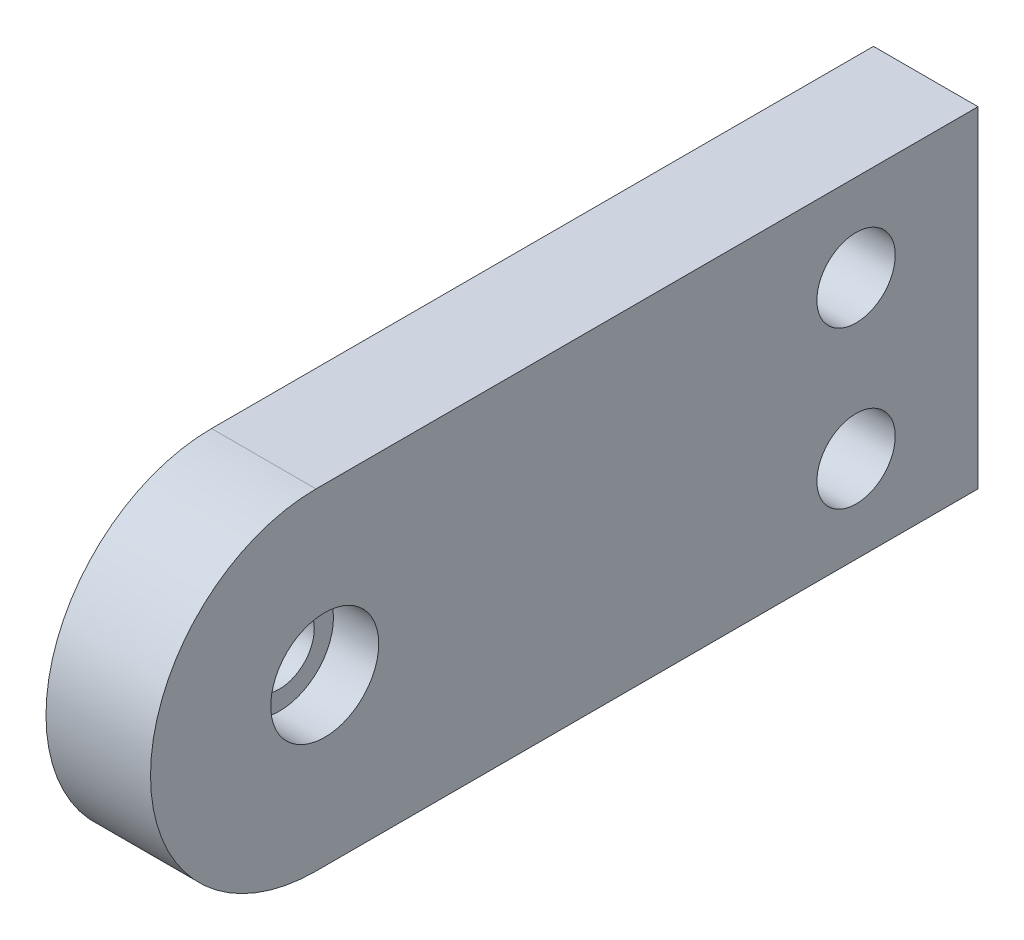
SolidWorks part; units mm, degrees
ref_plane "前视基准面" through (0, 0, 0) normal (0, 0, 1) x (1, 0, 0)
ref_plane "上视基准面" through (0, 0, 0) normal (0, 1, 0) x (1, 0, 0)
ref_plane "右视基准面" through (0, 0, 0) normal (1, 0, 0) x (0, 0, -1)
other "Configuration Table"
sketch "草图1" plane through (0, 0, 0) normal (1, 0, 0) x (0, 0, -1)
  line L0 (-150, 0) -> (150, 0) construction
  line L1 (-125, 14.5) -> (125, 14.5)
  line L2 (-125, 14.5) -> (-125, -14.5)
  line L3 (-125, -14.5) -> (125, -14.5)
  line L4 (125, 14.5) -> (125, -14.5)
  line L5 (-72.5, 29.5) -> (-72.5, 25.5)
  line L6 (-75, 14.5) -> (-45, 14.5)
  line L7 (-75, 14.5) -> (-75, 29.5)
  line L8 (-120, 10.8586) -> (120, 10.8586)
  line L9 (-120, 10.8586) -> (-120, -10.8586)
  line L10 (-120, -10.8586) -> (120, -10.8586)
  line L11 (120, 10.8586) -> (120, -10.8586)
  line L12 (-120, 10.8586) -> (120, -10.8586) construction
  line L13 (-120, -10.8586) -> (120, 10.8586) construction
  line L14 (-75, 29.5) -> (-45, 29.5)
  line L15 (-45, 14.5) -> (-45, 29.5)
  line L16 (-15, 14.5) -> (15, 14.5)
  line L17 (-15, 14.5) -> (-15, 29.5)
  line L18 (-15, 29.5) -> (15, 29.5)
  line L19 (15, 14.5) -> (15, 29.5)
  line L20 (45, 14.5) -> (75, 14.5)
  line L21 (45, 14.5) -> (45, 29.5)
  line L22 (45, 29.5) -> (75, 29.5)
  line L23 (75, 14.5) -> (75, 29.5)
  line L24 (-47.5, 29.5) -> (-47.5, 25.5)
  line L25 (-12.5, 29.5) -> (-12.5, 25.5)
  line L26 (12.5, 29.5) -> (12.5, 25.5)
  line L27 (47.5, 29.5) -> (47.5, 25.5)
  line L29 (72.5, 25.5) -> (72.5, 29.5)
  circle A2 centre (-67.5, -10.8586) radius 2
  circle A3 centre (-22.5, -10.8586) radius 2
  circle A4 centre (22.5, -10.8586) radius 2
  circle A5 centre (-60, 25.5) radius 2
  circle A6 centre (67.5, -10.8586) radius 2
  circle A7 centre (0, 25.5) radius 2
  circle A8 centre (60, 25.5) radius 2
  circle A9 centre (-60, 25.5) radius 12.5
  circle A10 centre (0, 25.5) radius 12.5
  circle A11 centre (60, 25.5) radius 12.5
  circle A12 centre (-67.5, -10.8586) radius 12.5
  circle A13 centre (-22.5, -10.8586) radius 12.5
  circle A14 centre (22.5, -10.8586) radius 12.5
  circle A15 centre (67.5, -10.8586) radius 12.5
  circle A16 centre (150, 0) radius 2
  circle A17 centre (-150, 0) radius 2
  circle A18 centre (-150, 0) radius 3.1
  point P10 (0, 0)
  point P12 (-125, 0)
  point P56 (-60, 29.5)
  point P62 (0, 29.5)
  point P64 (60, 29.5)
  dimension "D2" = 5
  dimension "D4" = 25
  dimension "D8" = 4
  dimension "D18" = 4
  dimension "D22" = 6.2
  dimension "D1" = 300
  dimension "D3" = 5
  dimension "D5" = 14.5
  dimension "D6" = 120
  dimension "D7" = 10.8586
  dimension "D9" = 52.5
  dimension "D10" = 45
  dimension "D11" = 45
  dimension "D12" = 45
  dimension "D13" = 60
  dimension "D14" = 60
  dimension "D15" = 60
  dimension "D16" = 60
  dimension "D17" = 52.5
  dimension "D19" = 30
  dimension "D20" = 4
  dimension "D21" = 15
extrude "凸台-拉伸1" add sketch "草图1" along normal blind 28 contours L1 L4 L3 L2 | L14 L15 L6 L7 | L18 L19 L16 L17 | L22 L23 L20 L21
extrude "切除-拉伸1" cut sketch "草图1<3>" along normal through all contours A2 | A3 | A4 | A6 | A8 | A7 | A5
sketch "草图1<3>" plane through (0, 0, 0) normal (1, 0, 0) x (0, 0, -1) same geometry as "草图1"
extrude "切除-拉伸2" cut sketch "草图1<5>" along normal offset from surface (24 mm away) 2 from offset 2 contours A9 L14 L5 | A9 L24 L14 | A10 L18 L25 | A10 L26 L18 | A11 L22 L27 | A11 L29 L22 | A12 | A9 | A13 | A10 | A14 | A11 | A15 region at (0, 28.5053, 72.3037) region at (0, 28.5053, 47.6963) region at (0, 28.5053, 12.3037) region at (0, 28.5053, -12.3037) region at (0, 28.5053, -47.6963) region at (0, 28.5053, -72.3037) up to face at (28, -10.8586, 65.5)
sketch "草图1<5>" plane through (0, 0, 0) normal (1, 0, 0) x (0, 0, -1) same geometry as "草图1"
sketch "草图3" plane through (0, 0, 125) normal (0, 0, 1) x (1, 0, 0)
  line L0 (28, 14.5) -> (28, -14.5) construction
  line L1 (28, 9.5) -> (22, 9.5)
  line L2 (28, 9.5) -> (28, -9.5)
  line L3 (28, -9.5) -> (22, -9.5)
  line L4 (22, 9.5) -> (22, -9.5)
  line L5 (28, 14.5) -> (0, 14.5) construction
  line L6 (28, -14.5) -> (0, -14.5) construction
  line L7 (0, 14.5) -> (0, -14.5) construction
  line L8 (0, 9.5) -> (6, 9.5)
  line L9 (0, 9.5) -> (0, -9.5)
  line L10 (0, -9.5) -> (6, -9.5)
  line L11 (6, 9.5) -> (6, -9.5)
  dimension "D1" = 6
  dimension "D2" = 5
  dimension "D3" = 5
extrude "凸台-拉伸2" add sketch "草图3" along normal blind 35 contours L1 L4 L3 L2
extrude "凸台-拉伸3" add sketch "草图3<3>" along normal blind 35 contours L2 L3 L4 L1 | L9 L10 L11 L8
sketch "草图3<3>" plane through (0, 0, 125) normal (0, 0, 1) x (1, 0, 0) same geometry as "草图3"
extrude "切除-拉伸3" cut sketch "草图1<6>" along normal through all contours A17
sketch "草图1<6>" plane through (0, 0, 0) normal (1, 0, 0) x (0, 0, -1) same geometry as "草图1"
extrude "切除-拉伸7" cut sketch "草图1<8>" along normal up to next contours A18
sketch "草图1<8>" plane through (0, 0, 0) normal (1, 0, 0) x (0, 0, -1) same geometry as "草图1"
fillet "圆角1" radius 9.5 4 edges at (25, 9.5, 160) (25, -9.5, 160) (3, -9.5, 160) (3, 9.5, 160)
fillet "圆角2" radius 5 2 edges at (14, -14.5, 125) (14, 14.5, 125)
sketch "草图4" plane through (0, 0, -125) normal (0, 0, -1) x (-1, 0, 0)
  line L1 (-28, 14.5) -> (0, 14.5) construction
  circle A0 centre (-14, 0) radius 5.1
  point P7 (-14, 14.5)
  dimension "D1" = 10.2
extrude "切除-拉伸4" cut sketch "草图4" against normal blind 31.5
extrude "切除-拉伸5" cut sketch "草图4<2>" against normal offset from surface (21.5 mm away) 10 flip side to cut up to face at (8.9, 0, -93.5)
sketch "草图4<2>" plane through (0, 0, -125) normal (0, 0, -1) x (-1, 0, 0) same geometry as "草图4"
sketch "草图5" plane through (0, 0, -103.5) normal (0, 0, -1) x (-1, 0, 0)
  line L0 (-28, 14.5) -> (0, 14.5) construction
  line L1 (-25.9, -12.4) -> (-2.1, -12.4)
  line L2 (-25.9, -12.4) -> (-25.9, 12.4)
  line L3 (-25.9, 12.4) -> (-2.1, 12.4)
  line L4 (-2.1, -12.4) -> (-2.1, 12.4)
  line L5 (-25.9, -12.4) -> (-2.1, 12.4) construction
  line L6 (-25.9, 12.4) -> (-2.1, -12.4) construction
  line L7 (0, -14.5) -> (0, 14.5) construction
  circle A0 centre (-14, 0) radius 5.1 construction
  point P0 (-14, 0)
  dimension "D1" = 2.1
  dimension "D2" = 2.1
extrude "切除-拉伸6" cut sketch "草图5" against normal blind 18 flip side to cut contours L3 L4 L1 L2
sketch "草图6" plane through (0, 14.5, 0) normal (0, 1, 0) x (1, 0, 0)
  circle A0 centre (7, 23.5) radius 0.75
  circle A1 centre (21, 35.5) radius 0.75
  circle A2 centre (7, -23.5) radius 0.75
  circle A3 centre (21, -35.5) radius 0.75
  dimension "D1" = 1.5
extrude "切除-拉伸8" cut sketch "草图6" against normal blind 4 contours A2 | A3 | A0 | A1
sketch "草图7" plane through (0, 14.5, 0) normal (0, 1, 0) x (1, 0, 0)
  circle A0 centre (7, -89.5) radius 0.75
  circle A1 centre (21.2, -110.5) radius 0.75
  dimension "D1" = 1.5
extrude "切除-拉伸9" cut sketch "草图7" against normal blind 4 contours A0 | A1
sketch "草图8" plane through (0, 0, 0) normal (-1, 0, 0) x (0, 0, 1)
  circle A0 centre (47, 4) radius 0.75
  circle A1 centre (2.499, -1.5) radius 0.75
  dimension "D1" = 1.5
extrude "切除-拉伸10" cut sketch "草图8" against normal blind 4
sketch "草图9" plane through (28, 0, 0) normal (1, 0, 0) x (0, 0, -1)
  circle A0 centre (-107.5, -0.5) radius 0.75
  circle A1 centre (-92.5, -0.5) radius 0.75
  dimension "D1" = 1.5
extrude "切除-拉伸11" cut sketch "草图9" against normal blind 4 contours A0 | A1
sketch "草图10" plane through (0, 0, 0) normal (-1, 0, 0) x (0, 0, 1)
  line L0 (30, 14.5) -> (0, -14.5)
  line L1 (45, 14.5) -> (15, 14.5) construction
  line L2 (120, -14.5) -> (-85.5, -14.5) construction
  line L3 (30, 14.5) -> (30, 45.5421)
  line L4 (30, 45.5421) -> (207.4503, 45.5421)
  line L5 (207.4503, 45.5421) -> (207.4503, -65.6361)
  line L6 (207.4503, -65.6361) -> (0, -65.6361)
  line L7 (0, -65.6361) -> (0, -14.5)
  line L8 (30, 45.5421) -> (-140.4585, 45.5421)
  line L9 (30, 14.5) -> (-10, 14.5)
  line L10 (30, 14.5) -> (30, -14.5)
  line L11 (30, -14.5) -> (-10, -14.5)
  line L12 (-10, 14.5) -> (-10, -14.5)
  line L13 (-140.4585, 45.5421) -> (-140.4585, -65.6361)
  line L14 (-140.4585, -65.6361) -> (-10, -65.6361)
  line L15 (-10, -65.6361) -> (-10, -14.5)
  circle M8 centre (2.499, -1.5) radius 0.75
  circle M12 centre (0, 25.5) radius 2
  circle M13 centre (-60, 25.5) radius 2
  circle M14 centre (-67.5, -10.8586) radius 2
  circle M15 centre (-22.5, -10.8586) radius 2
  line M17 (-85.5, 14.5) -> (-85.5, -14.5)
  line M18 (-85.5, -14.5) -> (120, -14.5)
  line M29 (45, 14.5) -> (15, 14.5)
  line M30 (15, 14.5) -> (15, 29.5)
  line M31 (15, 29.5) -> (-15, 29.5)
  line M32 (-15, 29.5) -> (-15, 14.5)
  line M33 (-15, 14.5) -> (-45, 14.5)
  line M34 (-45, 14.5) -> (-45, 29.5)
  line M35 (-45, 29.5) -> (-75, 29.5)
  line M36 (-75, 29.5) -> (-75, 14.5)
  line M37 (-75, 14.5) -> (-85.5, 14.5)
  dimension "D1" = 40
sketch "草图11" plane through (0, 0, 0) normal (1, 0, 0) x (0, 0, -1)
  line L0 (-30, 14.5) -> (0, -14.5) construction
  line L1 (-45, 14.5) -> (-15, 14.5) construction
  line L2 (-120, -14.5) -> (85.5, -14.5) construction
  circle A0 centre (-14.5301, 6.5) radius 0.75
  circle A1 centre (-1.0818, -6.5) radius 0.75
  circle A2 centre (-14.5301, 6.5) radius 2.5
  circle A3 centre (-1.0818, -6.5) radius 2.5
  circle A4 centre (-14.5301, 6.5) radius 1.8
  circle A5 centre (-1.0818, -6.5) radius 1.8
  circle A6 centre (5.4699, 6.5) radius 0.75
  circle A7 centre (5.4699, 6.5) radius 2.5
  circle A8 centre (5.4699, 6.5) radius 1.8
  dimension "D3" = 1.5
  dimension "D4" = 3.6
  dimension "D5" = 5
  dimension "D1" = 5
  dimension "D2" = 5
  dimension "D6" = 8
  dimension "D7" = 8
  dimension "D8" = 20
extrude "切除-拉伸12" cut sketch "草图11" along normal through all contours A1 | A0 | A6
extrude "切除-拉伸14" cut sketch "草图10" against normal through all contours L14 L15 L3 L8 L13 M18 M17 M37 M36 M35 M34 M33 M32 M31 M30 M29 | L12 L9 M30 M31 M32 M33 M34 M35 M36 M37 M17 M18 M12 M14 M15 M13 region at (0, 16.5351, 22.5) region at (0, 6.3937, -42.6633)
extrude "切除-拉伸15" cut sketch "草图10<5>" against normal blind 4.1 contours L9 L12 L0 M18 M29 M8 region at (0, 2.9108, 4.0037)
sketch "草图10<5>" plane through (0, 0, 0) normal (-1, 0, 0) x (0, 0, 1) same geometry as "草图10"
extrude "切除-拉伸16" cut sketch "草图10<6>" along normal blind 4.1 from surface contours L9 L12 L0 M18 M29 M8 | M8 region at (0, 2.9108, 4.0037) region at (0, -1.5, 2.499) starting at face at (28, 6.7692, 90.5389)
sketch "草图10<6>" plane through (0, 0, 0) normal (-1, 0, 0) x (0, 0, 1) same geometry as "草图10"
sketch "草图13" plane through (0, 14.5, 0) normal (0, 1, 0) x (1, 0, 0)
  line L0 (4.1, -30) -> (0, -30) construction
  line L1 (4.1, -30) -> (23.9, -30)
  line L2 (4.1, -30) -> (4.1, 10)
  line L3 (4.1, 10) -> (23.9, 10)
  line L4 (23.9, -30) -> (23.9, 10)
  line L5 (4.1, -30) -> (4.1, -5.9372) construction
extrude "切除-拉伸17" cut sketch "草图13" against normal blind 4.1
sketch "草图14" plane through (0, -14.5, 0) normal (0, -1, 0) x (1, 0, 0)
  line L0 (4.1, 0) -> (0, 0) construction
  line L1 (4.1, 0) -> (23.9, 0)
  line L2 (4.1, 0) -> (4.1, -10)
  line L3 (4.1, -10) -> (23.9, -10)
  line L4 (23.9, 0) -> (23.9, -10)
  line L5 (4.1, -10) -> (4.1, 0) construction
extrude "切除-拉伸18" cut sketch "草图14" against normal blind 4.1
sketch "草图15" plane through (0, 0, 0) normal (-1, 0, 0) x (0, 0, 1)
  line L0 (0, -10.4) -> (0, -14.5)
  line L1 (0, -14.5) -> (4.2414, -10.4)
  line L2 (30, 14.5) -> (0, -14.5) construction
  line L4 (4.2414, -10.4) -> (0, -10.4)
  line L5 (0, -10.4) -> (-10, -10.4) construction
extrude "切除-拉伸19" cut sketch "草图15" against normal through all
sketch "草图16" plane through (0, 29.5, 0) normal (0, 1, 0) x (1, 0, 0)
  line L0 (28, -75) -> (0, -75) construction
  line L1 (6, -77.5) -> (22, -77.5)
  line L2 (6, -77.5) -> (6, -72.5)
  line L3 (6, -72.5) -> (22, -72.5)
  line L4 (22, -77.5) -> (22, -72.5)
  line L5 (6, -77.5) -> (22, -72.5) construction
  line L6 (6, -72.5) -> (22, -77.5) construction
  line L7 (26, -72.5) -> (2, -72.5) construction
  line L8 (26, -47.5) -> (26, -72.5) construction
  line L9 (6, -72.5) -> (22, -72.5)
  line L10 (6, -72.5) -> (6, -60)
  line L11 (6, -60) -> (22, -60)
  line L12 (22, -72.5) -> (22, -60)
  point P0 (14, -75)
  point P7 (14, -75)
  point P14 (26, -60)
  line M10 (0, -75) -> (28, -75)
  line M13 (26, -72.5) -> (2, -72.5)
  dimension "D1" = 16
extrude "切除-拉伸20" cut sketch "草图16" against normal blind 3 contours L1 L4 L2 M10 | L4 L2 M10 M13 | L12 L11 L10 M13 region at (14, 29.5, 76.25) region at (14, 29.5, 73.75) region at (14, 29.5, 66.25)
sketch "草图18" plane through (28, 0, 0) normal (1, 0, 0) x (0, 0, -1)
  line L0 (-150.5, 9.5) -> (-125, 9.5) construction
  line L1 (-160, 9.5) -> (-112.5, 9.5)
  line L2 (-160, 9.5) -> (-160, -9.5)
  line L3 (-160, -9.5) -> (-112.5, -9.5)
  line L4 (-112.5, 9.5) -> (-112.5, -9.5)
  line L5 (-150.5, -9.5) -> (-125, -9.5) construction
  arc A0 (-150.5, 9.5) -> (-160, 0) centre (-150.5, 0) ccw construction
  circle A1 centre (-107.5, -0.5) radius 0.75 construction
  circle A2 centre (-119.5, 4.5) radius 1.5
  circle A3 centre (-119.5, 4.5) radius 0.75
  circle A4 centre (-119.5, 4.5) radius 2.25
  circle A5 centre (-119.5, -4.5) radius 0.75
  circle A6 centre (-119.5, -4.5) radius 1.5
  circle A7 centre (-119.5, -4.5) radius 2.25
  dimension "D1" = 5
  dimension "D2" = 4.5
  dimension "D3" = 3
  dimension "D4" = 1.5
  dimension "D5" = 7
  dimension "D6" = 5
  dimension "D7" = 5
extrude "切除-拉伸21" cut sketch "草图18" against normal through all flip side to cut contours L1 L4 L3 L2
extrude "切除-拉伸22" cut sketch "草图18<4>" against normal through all from surface contours L1 L4 L3 L2 starting at face at (22, 2, 150)
sketch "草图18<4>" plane through (28, 0, 0) normal (1, 0, 0) x (0, 0, -1) same geometry as "草图18"
extrude "切除-拉伸23" cut sketch "草图18<5>" against normal through all contours A2 | A6
sketch "草图18<5>" plane through (28, 0, 0) normal (1, 0, 0) x (0, 0, -1) same geometry as "草图18"
extrude "切除-拉伸24" cut sketch "草图18<6>" against normal offset from surface (4 mm away) 2 contours A4 | A7 up to face at (22, 4.5, 118)
sketch "草图18<6>" plane through (28, 0, 0) normal (1, 0, 0) x (0, 0, -1) same geometry as "草图18"
sketch "草图17" plane through (28, 0, 0) normal (1, 0, 0) x (0, 0, -1)
  line L5 (-200, -100) -> (200, 100) construction
  line L6 (-200, 100) -> (200, -100) construction
  circle A0 centre (-150, 0) radius 3.1
  point P0 (0, 0)
  dimension "D3" = 6.2
  dimension "D1" = 400
  dimension "D2" = 200
extrude "切除-拉伸25" cut sketch "草图17" against normal blind 2.6 contours A0
